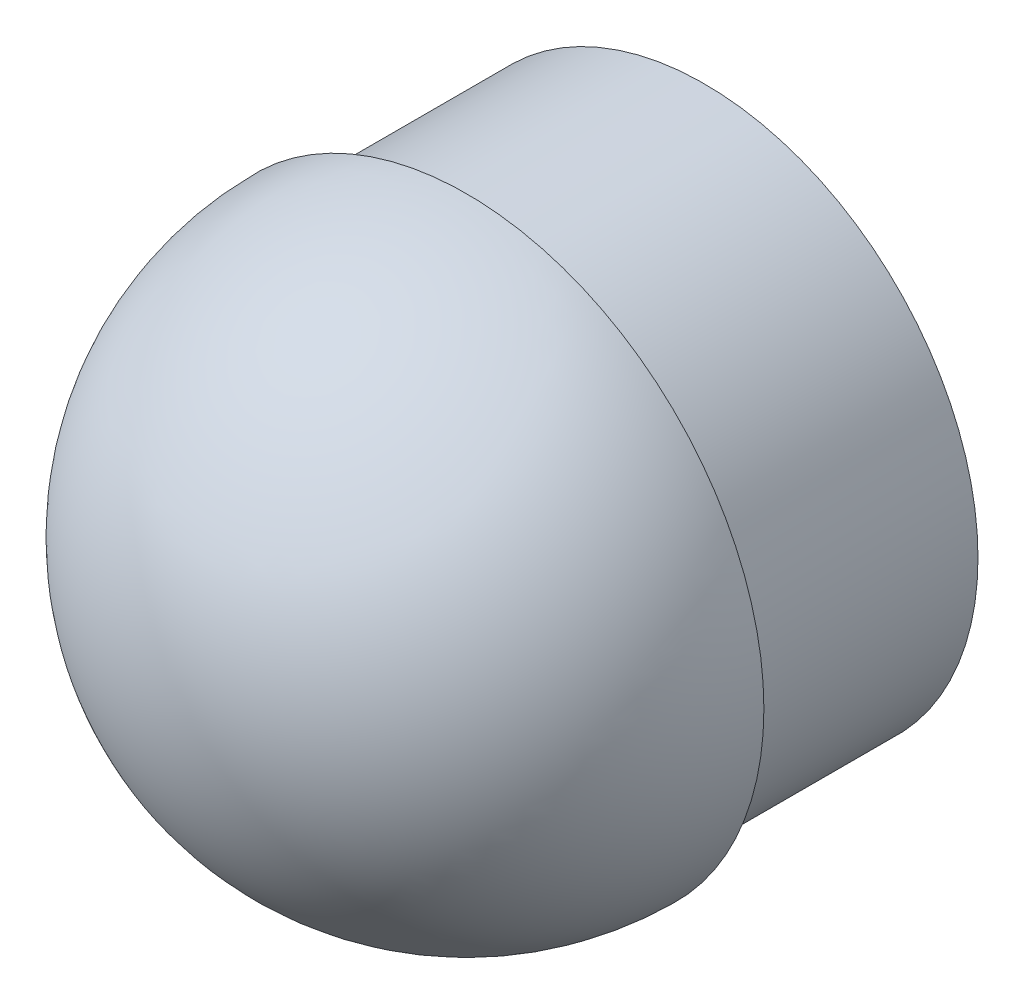
SolidWorks part; units mm, degrees
ref_plane "Front Plane" through (0, 0, 0) normal (0, 0, 1) x (1, 0, 0)
ref_plane "Top Plane" through (0, 0, 0) normal (0, 1, 0) x (1, 0, 0)
ref_plane "Right Plane" through (0, 0, 0) normal (1, 0, 0) x (0, 0, -1)
sketch "Sketch1" plane through (0, 0, 0) normal (0, 0, 1) x (1, 0, 0)
  circle A0 centre (0, 0) radius 11.5
  dimension "D1" = 23
extrude "Boss-Extrude1" add sketch "Sketch1" along normal blind 10
sketch "Sketch2" plane through (0, 0, 10) normal (0, 0, 1) x (1, 0, 0)
  circle A0 centre (0, 0) radius 12.5
  dimension "D1" = 25
extrude "Boss-Extrude2" add sketch "Sketch2" along normal blind 12.5
fillet "Fillet1" radius 12.5 1 edges at (12.5, 0, 22.5)
